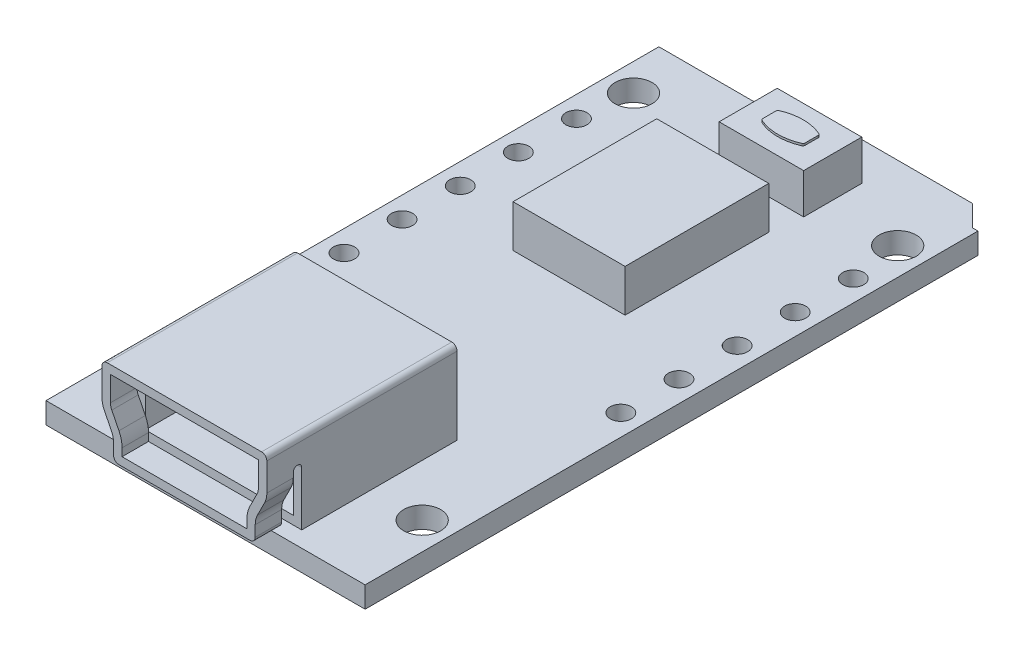
SolidWorks part; units mm, degrees
ref_plane "Front Plane" through (0, 0, 0) normal (0, 0, 1) x (1, 0, 0)
ref_plane "Top Plane" through (0, 0, 0) normal (0, 1, 0) x (1, 0, 0)
ref_plane "Right Plane" through (0, 0, 0) normal (1, 0, 0) x (0, 0, -1)
sketch "Sketch1" plane through (0, 0, 0) normal (0, 1, 0) x (1, 0, 0)
  line L0 (-7.55, 14) -> (-1.95, 14)
  line L1 (-7.55, -15) -> (7.55, -15)
  line L2 (-7.55, -15) -> (-7.55, 14)
  line L3 (-0.95, 15) -> (6.3, 15)
  line L4 (7.55, -15) -> (7.55, 14)
  line L5 (-7.55, -15) -> (7.55, 15) construction
  line L6 (-7.55, 15) -> (7.55, -15) construction
  line L7 (-1.95, 14) -> (-0.95, 15)
  line L8 (7.55, 14) -> (7.3, 14)
  line L9 (-6.25, -11) -> (6.25, -11) construction
  line L10 (0, -11) -> (0, -15) construction
  line L11 (7.3, 14) -> (6.3, 15)
  line L12 (7.55, 15) -> (-7.55, 15) construction
  line L13 (-7.55, 15) -> (-7.55, 14) construction
  line L14 (7.55, 15) -> (7.55, 14) construction
  line L15 (-6.25, 11.5) -> (6.25, 11.5) construction
  line L16 (0, 0) -> (0, 11.5) construction
  line L17 (-6.55, 9.1) -> (-6.55, -1.9) construction
  circle A0 centre (-6.25, 11.5) radius 0.875
  circle A1 centre (6.25, 11.5) radius 0.875
  circle A2 centre (-6.25, -11) radius 0.875
  circle A3 centre (6.25, -11) radius 0.875
  circle A4 centre (-6.55, 9.1) radius 0.5
  circle A5 centre (-6.55, -1.9) radius 0.5
  circle A6 centre (-6.55, 3.6) radius 0.5
  circle A7 centre (-6.55, 6.35) radius 0.5
  circle A8 centre (-6.55, 0.85) radius 0.5
  circle A9 centre (6.55, -1.9) radius 0.5
  circle A10 centre (6.55, 0.85) radius 0.5
  circle A11 centre (6.55, 3.6) radius 0.5
  circle A12 centre (6.55, 6.35) radius 0.5
  circle A13 centre (6.55, 9.1) radius 0.5
  point P0 (0, 0)
  dimension "D3" = 1.75
  dimension "D4" = 1.75
  dimension "D10" = 1.75
  dimension "D11" = 1.75
  dimension "D19" = 1
  dimension "D20" = 1
  dimension "D21" = 1
  dimension "D22" = 1
  dimension "D23" = 1
  dimension "D1" = 15.1
  dimension "D2" = 30
  dimension "D5" = 1.25
  dimension "D6" = 1
  dimension "D7" = 135
  dimension "D8" = 7.25
  dimension "D9" = 135
  dimension "D12" = 12.5
  dimension "D13" = 2.5
  dimension "D14" = 12.5
  dimension "D15" = 4
  dimension "D16" = 2.75
  dimension "D17" = 2.75
  dimension "D18" = 2.75
  dimension "D24" = 1
  dimension "D25" = 9.1
extrude "Boss-Extrude1" add sketch "Sketch1" along normal blind 1
sketch "Sketch2" plane through (0, 0, 15) normal (0, 0, 1) x (1, 0, 0)
  line L0 (0, 0) -> (0, 6.0411) construction
  line L1 (3.35, 1.1) -> (3.35, 2.1)
  line L2 (3.35, 2.1) -> (3.9, 3.2)
  line L3 (3.9, 3.2) -> (3.9, 5)
  line L4 (-7.55, 0) -> (7.55, 0) construction
  line L5 (-3.35, 1.1) -> (-3.35, 2.1)
  line L6 (-3.35, 2.1) -> (-3.9, 3.2)
  line L7 (-3.9, 3.2) -> (-3.9, 5)
  line L8 (-3.9, 5) -> (3.9, 5)
  line L9 (-3.35, 1.1) -> (3.35, 1.1)
  dimension "D1" = 7.8
  dimension "D2" = 3.9
  dimension "D3" = 6.7
  dimension "D4" = 5
  dimension "D5" = 1
  dimension "D6" = 1.8
extrude "Boss-Extrude2" add sketch "Sketch2" along normal blind 1 and the other way blind 0.25 separate body
sketch "Sketch3" plane through (0, 0, 14.75) normal (0, 0, -1) x (-1, 0, 0)
  line L0 (3.35, 1.1) -> (-3.35, 1.1) construction
  line L1 (-3.9, 1.1) -> (3.9, 1.1)
  line L2 (-3.9, 1.1) -> (-3.9, 5)
  line L3 (-3.9, 5) -> (3.9, 5)
  line L4 (3.9, 1.1) -> (3.9, 5)
  line L5 (-3.9, 1.1) -> (3.9, 5) construction
  line L6 (-3.9, 5) -> (3.9, 1.1) construction
  point P0 (0, 3.05)
extrude "Boss-Extrude3" add sketch "Sketch3" along normal blind 7.75
fillet "Fillet1" radius 0.25 4 edges at (3.9, 5, 11.5) (-3.9, 5, 11.5)
fillet "Fillet2" radius 1 4 edges at (3.35, 2.1, 15.375) (-3.35, 2.1, 15.375)
shell "Shell1" thickness 0.4 removed face at (0, 2.85, 16)
sketch "Sketch5" plane through (3.9, 0, 0) normal (1, 0, 0) x (0, 0, -1)
  line L1 (-14.75, 1.1) -> (-14.35, 1.1)
  line L2 (-14.75, 1.1) -> (-14.75, 3.66)
  line L3 (-14.56, 3.85) -> (-14.54, 3.85)
  line L4 (-14.35, 1.1) -> (-14.35, 3.66)
  arc A0 (-14.54, 3.85) -> (-14.35, 3.66) centre (-14.54, 3.66) cw
  arc A1 (-14.75, 3.66) -> (-14.56, 3.85) centre (-14.56, 3.66) cw
  point P7 (-14.35, 3.85)
  point P10 (-14.75, 3.85)
  dimension "D3" = 0.19
  dimension "D1" = 0.4
  dimension "D2" = 2.75
extrude "Cut-Extrude1" cut sketch "Sketch5" against normal blind 8.75
sketch "Sketch6" plane through (0, 1, 0) normal (0, 1, 0) x (1, 0, 0)
  line L0 (0, 0) -> (0, 5.6) construction
  line L1 (6.3, 15) -> (-0.95, 15) construction
  line L2 (-2.65, 2.2) -> (2.65, 2.2)
  line L3 (-2.65, 2.2) -> (-2.65, 9)
  line L4 (-2.65, 9) -> (2.65, 9)
  line L5 (2.65, 2.2) -> (2.65, 9)
  line L6 (-2.65, 2.2) -> (2.65, 9) construction
  line L7 (-2.65, 9) -> (2.65, 2.2) construction
  dimension "D1" = 6.8
  dimension "D2" = 5.3
  dimension "D3" = 12.8
extrude "Boss-Extrude4" add sketch "Sketch6" along normal blind 2 separate body
sketch "Sketch7" plane through (0, 1, 0) normal (0, 1, 0) x (1, 0, 0)
  line L0 (6.3, 15) -> (-0.95, 15) construction
  line L1 (-1.15, 13.2) -> (2.85, 13.2)
  line L2 (-1.15, 13.2) -> (-1.15, 10.45)
  line L3 (-1.15, 10.45) -> (2.85, 10.45)
  line L4 (2.85, 13.2) -> (2.85, 10.45)
  line L5 (7.55, -15) -> (7.55, 14) construction
  dimension "D1" = 4
  dimension "D2" = 2.75
  dimension "D3" = 1.8
  dimension "D4" = 4.7
extrude "Boss-Extrude5" add sketch "Sketch7" along normal blind 1.9 separate body
sketch "Sketch8" plane through (0, 2.9, 0) normal (0, 1, 0) x (1, 0, 0)
  line L0 (-0.15, 12.2) -> (-0.15, 11.45)
  line L1 (1.85, 12.2) -> (1.85, 11.45)
  line L2 (-0.15, 11.825) -> (1.85, 11.825) construction
  line L3 (0.85, 10.45) -> (0.85, 13.2) construction
  line L4 (-1.15, 10.45) -> (2.85, 10.45) construction
  line L5 (2.85, 13.2) -> (-1.15, 13.2) construction
  line L6 (0.85, 12.425) -> (0.85, 11.225) construction
  arc A0 (-0.15, 12.2) -> (1.85, 12.2) centre (0.85, 10.0903) cw
  arc A1 (-0.15, 11.45) -> (1.85, 11.45) centre (0.85, 13.5597) ccw
  point P13 (0.85, 11.825)
  dimension "D4" = 1.2
  dimension "D1" = 2
  dimension "D2" = 0.75
  dimension "D3" = 0.75
extrude "Boss-Extrude6" add sketch "Sketch8" along normal up to surface (0.1 mm away) separate body up to face at (0, 3, -5.6)
fillet "Fillet3" radius 0.1 4 edges at (-0.15, 2.95, -11.45) (-0.15, 2.95, -12.2) (1.85, 2.95, -12.2) (1.85, 2.95, -11.45)
